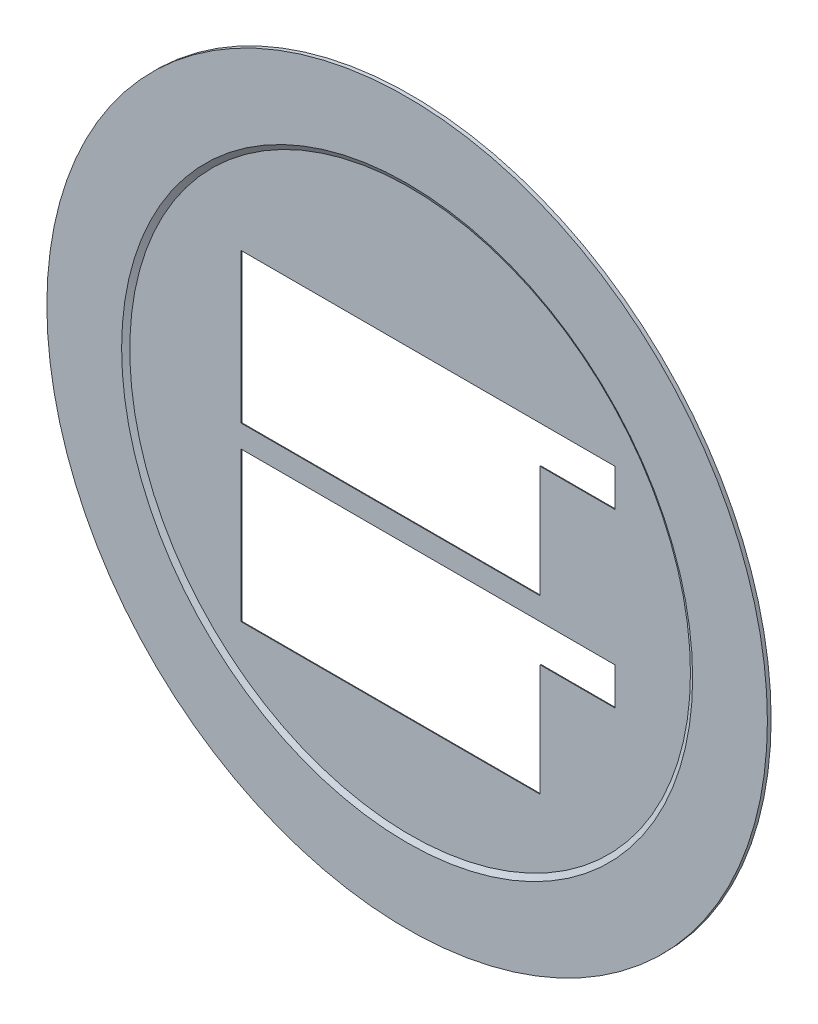
SolidWorks part; units mm, degrees
ref_plane "Front Plane" through (0, 0, 0) normal (1, 0, 0) x (0, 1, 0)
ref_plane "Top Plane" through (0, 0, 0) normal (0, 0, 1) x (0, 1, 0)
ref_plane "Right Plane" through (0, 0, 0) normal (0, 1, 0) x (-1, 0, 0)
sketch "Sketch2" plane through (0, 0, 0) normal (1, 0, 0) x (0, 1, 0)
  line L0 (48.1928, 0.5) -> (38.1928, 0.5)
  line L1 (38.1928, 0.5) -> (37.5, 0.1)
  line L2 (37.5, 0.1) -> (0, 0.1)
  line L3 (0, 0.1) -> (0, 0)
  line L4 (0, 0) -> (48.1928, 0)
  line L5 (48.1928, 0) -> (48.1928, 0.5)
  point P4 (39.2867, 0.5)
  dimension "D1" = 0.1
  dimension "D2" = 37.5
  dimension "D3" = 10
  dimension "D4" = 0.5
  dimension "D5" = 30
ref_axis "Axis1" through (0, 0, 0.1) along (0, 0, -1)
revolve "Revolve1" add sketch "Sketch2" angle 360 about L3
sketch "Sketch3" plane through (0, 0, 0.1) normal (0, 0, 1) x (1, 0, 0)
  line L0 (-22.6056, 18.919) -> (-36.4225, 31.5586) construction
  line L1 (-22.6056, 18.919) -> (17.3944, 18.919)
  line L2 (-22.6056, 18.919) -> (-22.6056, -1.081)
  line L3 (-22.6056, -1.081) -> (17.3944, -1.081)
  line L4 (17.3944, 18.919) -> (17.3944, -1.081)
  line L5 (-22.6056, -4.081) -> (17.3944, -4.081)
  line L6 (-22.6056, -4.081) -> (-22.6056, -24.081)
  line L7 (-22.6056, -24.081) -> (17.3944, -24.081)
  line L8 (17.3944, -4.081) -> (17.3944, -24.081)
  line L9 (17.3944, 18.919) -> (27.3944, 18.919)
  line L10 (17.3944, 18.919) -> (17.3944, 13.919)
  line L11 (17.3944, 13.919) -> (27.3944, 13.919)
  line L12 (27.3944, 18.919) -> (27.3944, 13.919)
  line L13 (17.3944, -4.081) -> (27.3944, -4.081)
  line L14 (17.3944, -4.081) -> (17.3944, -9.081)
  line L15 (17.3944, -9.081) -> (27.3944, -9.081)
  line L16 (27.3944, -4.081) -> (27.3944, -9.081)
  line L17 (17.3944, -24.081) -> (31.2114, -36.7205) construction
  line L18 (-22.6056, -24.081) -> (-32.8414, -35.2702) construction
  line L19 (27.3944, 18.919) -> (37.6302, 30.1083) construction
  circle A0 centre (0, 0) radius 48.1928 construction
  dimension "D1" = 20
  dimension "D2" = 3
  dimension "D3" = 40
  dimension "D4" = 10
  dimension "D5" = 5
extrude "Cut-Extrude1" cut sketch "Sketch3" against normal through all contours L4 L1 L2 L3 | L12 L9 L4 L11 | L8 L5 L6 L7 | L16 L13 L8 L15 region at (-2.6056, 8.919, 0.1) region at (22.3944, 16.419, 0.1) region at (-2.6056, -14.081, 0.1) region at (22.3944, -6.581, 0.1)
